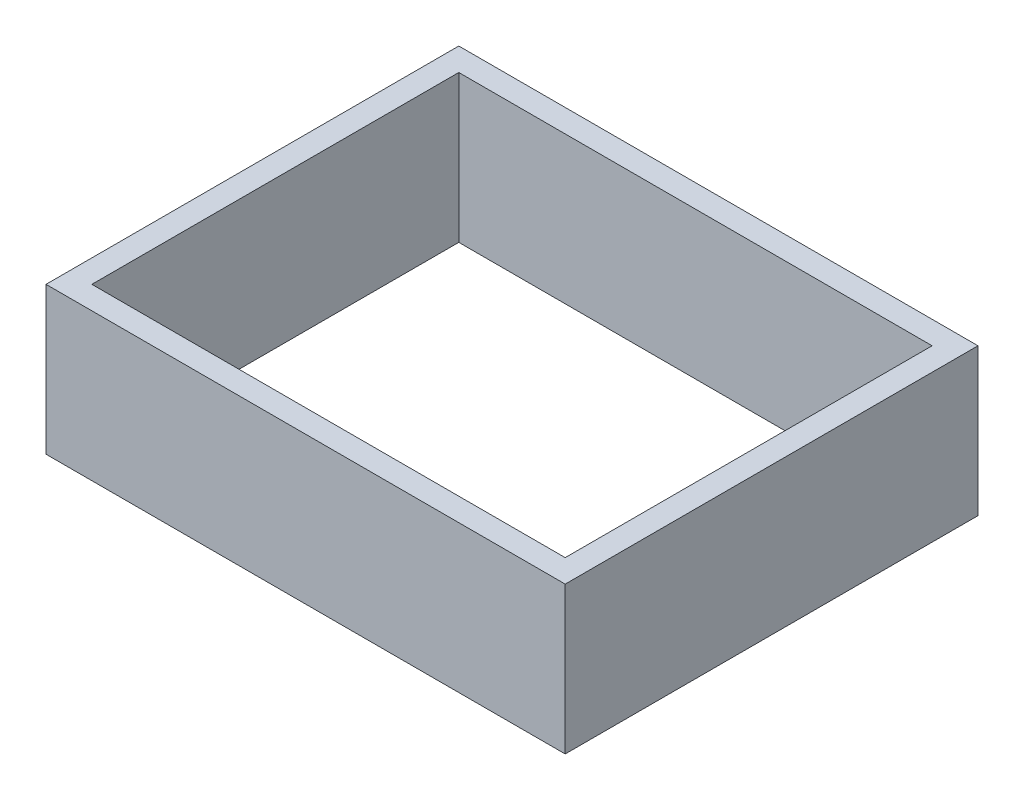
SolidWorks part; units mm, degrees
ref_plane "Front Plane" through (0, 0, 0) normal (0, 0, 1) x (1, 0, 0)
ref_plane "Top Plane" through (0, 0, 0) normal (0, 1, 0) x (1, 0, 0)
ref_plane "Right Plane" through (0, 0, 0) normal (1, 0, 0) x (0, 0, -1)
sketch "Sketch1" plane through (0, 0, 0) normal (0, 1, 0) x (1, 0, 0)
  line L1 (0, 0) -> (283, 0)
  line L2 (0, 0) -> (0, 225)
  line L3 (0, 225) -> (283, 225)
  line L4 (283, 0) -> (283, 225)
  dimension "D1" = 225
  dimension "D2" = 283
extrude "Boss-Extrude1" add sketch "Sketch1" along normal blind 80.2 contours L1 L4 L3 L2
sketch "Sketch2" plane through (0, 80.2, 0) normal (0, 1, 0) x (1, 0, 0)
  line L14 (12.5, 12.5) -> (270.5, 12.5)
  line L15 (270.5, 12.5) -> (270.5, 212.5)
  line L16 (270.5, 212.5) -> (12.5, 212.5)
  line L17 (12.5, 212.5) -> (12.5, 12.5)
  line L18 (12.5, 12.5) -> (270.5, 12.5)
  line L19 (270.5, 12.5) -> (270.5, 212.5)
  line L20 (270.5, 212.5) -> (12.5, 212.5)
  line L21 (12.5, 212.5) -> (12.5, 12.5)
  dimension "D1" = 12.5
extrude "Cut-Extrude1" cut sketch "Sketch2" against normal up to surface (80.2 mm away) contours L21 L18 L19 L20 up to face at (141.5, 0, -112.5)
equation "\"Length\"= 283"
equation "\"Width\"= 225"
equation "\"WallThickness\"= 12.5"
equation "\"UpperWaterJacketThickness\"= 28"
equation "\"D1@Sketch1\"=\"Width\""
equation "\"D2@Sketch1\"=\"Length\""
equation "\"SpacerHeight\"= 80.2"
equation "\"D1@Boss-Extrude1\"=\"SpacerHeight\""
equation "\"D1@Sketch2\"=\"WallThickness\""
